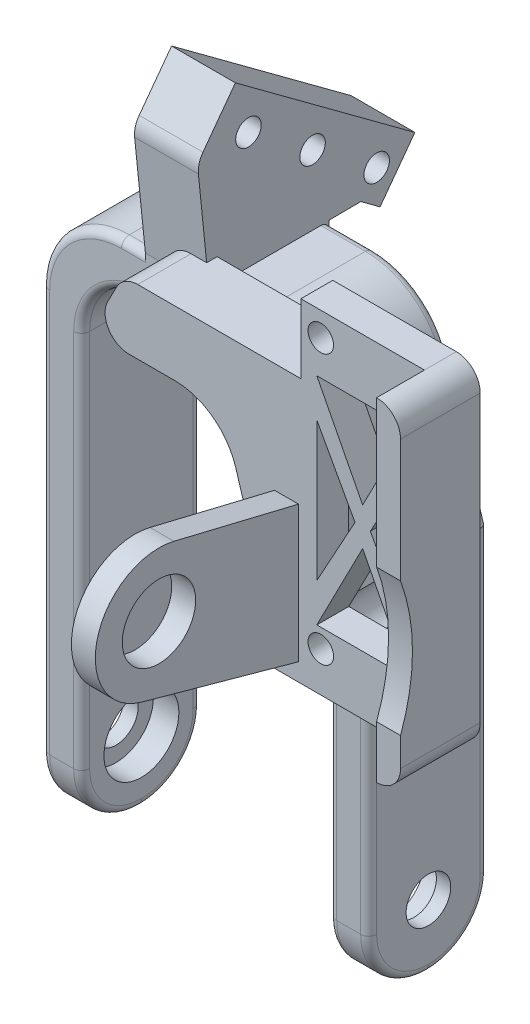
SolidWorks part; units mm, degrees
ref_plane "前视基准面" through (0, 0, 0) normal (0, 0, 1) x (1, 0, 0)
ref_plane "上视基准面" through (0, 0, 0) normal (0, 1, 0) x (1, 0, 0)
ref_plane "右视基准面" through (0, 0, 0) normal (1, 0, 0) x (0, 0, -1)
sketch "草图1" plane through (0, 0, 0) normal (0, 1, 0) x (1, 0, 0)
  line L1 (24, 7.5) -> (-17, 7.5)
  line L2 (24, 7.5) -> (24, -7.5)
  line L3 (24, -7.5) -> (-17, -7.5)
  line L4 (-17, 7.5) -> (-17, -7.5)
  line L5 (24, 7.5) -> (-17, -7.5) construction
  line L6 (24, -7.5) -> (-17, 7.5) construction
  point P0 (0, 0)
extrude "凸台-拉伸1" add sketch "草图1" against normal blind 68
sketch "草图3" plane through (0, 0, 7.5) normal (0, 0, 1) x (1, 0, 0)
  line L0 (-17, -68) -> (24, -68) construction
  line L1 (-12, -68) -> (19, -68)
  line L2 (-12, -68) -> (-12, -5)
  line L3 (-12, -5) -> (12.6087, -5)
  line L4 (19, -68) -> (19, -25.9143)
  line L5 (12.6087, -5) -> (19, -25.9143)
  line L6 (17, 0) -> (27.4891, -34.3238)
  line L7 (17, 0) -> (27.4891, 0)
  line L8 (27.4891, 0) -> (27.4891, -34.3238)
  line L9 (-17, 0) -> (24, 0) construction
  line L10 (-17, 0) -> (24, 0) construction
extrude "切除-拉伸1" cut sketch "草图3" against normal through all
fillet "圆角1" radius 8 3 edges at (-12, -5, 0) (19, -25.9143, 0) (12.6087, -5, 0)
fillet "圆角3" radius 7.5 4 edges at (21.5, -68, -7.5) (21.5, -68, 7.5) (-14.5, -68, -7.5) (-14.5, -68, 7.5)
sketch "草图4" plane through (24, 0, 0) normal (1, 0, 0) x (0, 0, -1)
  circle A0 centre (0, -60) radius 2.8
extrude "切除-拉伸2" cut sketch "草图4" against normal through all
sketch "草图6" plane through (19, 0, 0) normal (1, 0, 0) x (0, 0, -1)
  circle A0 centre (0, -60) radius 4.7
extrude "切除-拉伸4" cut sketch "草图6" along normal blind 3.2
ref_plane "基准面1" through (3.5, 0, 0) normal (1, 0, 0) x (0, 0, -1)
mirror "镜向2" about plane through (3.5, 0, 0) normal (1, 0, 0) of "切除-拉伸4"
sketch "草图7" plane through (0, 0, 0) normal (1, 0, 0) x (0, 0, -1)
  line L0 (-6.5933, 17.6444) -> (9.4891, 5.7551) construction
  line L2 (-8.9711, 14.4279) -> (-4.2154, 20.8609)
  line L3 (-4.2154, 20.8609) -> (18.3, 4.2159)
  line L5 (7.5, 0) -> (7.5, -22.9063) construction
  line L6 (7.5, 0) -> (7.5, -22.9063) construction
  line L8 (-7.5, 0) -> (7.5, 0)
  line L9 (-7.5, -5) -> (7.5, -5) construction
  line L10 (-7.5, -5) -> (7.5, -5) construction
  line L15 (7.5, 3.0644) -> (7.5, 0)
  line L16 (-8.9711, 14.4279) -> (-7.5, 0)
  line L17 (7.5, 3.0644) -> (13.933, -1.6913)
  line L18 (18.3, 4.2159) -> (13.933, -1.6913)
  circle A2 centre (5.4685, 8.7275) radius 1.6
  circle A3 centre (-2.5727, 14.6721) radius 1.6
  circle A4 centre (13.5098, 2.7828) radius 1.6
  dimension "D1" = 10
  dimension "D2" = 3.2
  dimension "D3" = 3.2
  dimension "D9" = 10
  dimension "D4" = 3
  dimension "D5" = 5
  dimension "D6" = 4
  dimension "D7" = 3.3461
  dimension "D8" = 3.0644
extrude "凸台-拉伸2" add sketch "草图7" along normal mid plane 8
chamfer "倒角1" distance 3 distance2 5 1 edges at (0, 3.0644, -7.5) first distance on face at (4.7083, -20.0817, -7.5)
fillet "圆角4" radius 10 2 edges at (17, 0, 0) (-17, 0, 0)
fillet "圆角2" radius 1 36 edges at (-17, -35.25, -7.5) (24, -41.7031, -7.5) (24, -41.7031, 7.5) (-17, -35.25, 7.5) (-9.6569, -7.3431, 7.5) (1.3441, -5, 7.5) (19, -43.8047, 7.5) (19, -43.8047, -7.5) (1.3441, -5, -7.5) (-9.6569, -7.3431, -7.5) (-12, -36.75, -7.5) (-12, -36.75, 7.5) (19, -65.8033, 5.3033) (19, -65.8033, -5.3033) (-12, -65.8033, -5.3033) (-12, -65.8033, 5.3033) (-17, -65.8033, 5.3033) (-17, -65.8033, -5.3033) (24, -65.8033, -5.3033) (24, -65.8033, 5.3033) (11.4473, -6.5694, 7.5) (16.4949, -17.7167, 7.5) (18.9122, -25.9274, 7.5) (18.9122, -25.9274, -7.5) (16.4949, -17.7167, -7.5) (11.4473, -6.5694, -7.5) (21.5814, -14.9919, -7.5) (21.5814, -14.9919, 7.5) (6.7997, 0, -7.5) (15.5481, -1.9618, -7.5) (6.7997, 0, 7.5) (15.5481, -1.9618, 7.5) (-5.5, 0, -7.5) (-14.0711, -2.9289, -7.5) (-5.5, 0, 7.5) (-14.0711, -2.9289, 7.5)
sketch "草图16" plane through (0, 0, 7.5) normal (0, 0, 1) x (1, 0, 0)
  line L0 (6.6883, -5) -> (-4, -5) construction
  line L1 (18.6507, -24.7714) -> (14.339, -10.662) construction
  line L2 (19, -60.5) -> (19, -27.1094) construction
  line L3 (24, -22.9063) -> (24, -60.5) construction
  line L4 (19.1628, -7.0775) -> (24, -22.9063) construction
  line L5 (4, 0) -> (9.5994, 0) construction
  line L6 (6.6883, -5) -> (4, -5)
  line L7 (18.6507, -24.7714) -> (14.339, -10.662)
  line L8 (19, -32.1919) -> (19, -27.1094)
  line L9 (24, -22.9063) -> (24, -32.1919)
  line L10 (19.1628, -7.0775) -> (24, -22.9063)
  line L11 (4, 0) -> (9.5994, 0)
  line L12 (4, 0) -> (4, -5)
  line L13 (19, -32.1919) -> (24, -32.1919)
  arc A0 (14.339, -10.662) -> (6.6883, -5) centre (6.6883, -13) ccw construction
  arc A1 (19, -27.1094) -> (18.6507, -24.7714) centre (11, -27.1094) ccw construction
  arc A2 (19.1628, -7.0775) -> (9.5994, 0) centre (9.5994, -10) ccw construction
  arc A3 (14.339, -10.662) -> (6.6883, -5) centre (6.6883, -13) ccw
  arc A4 (19, -27.1094) -> (18.6507, -24.7714) centre (11, -27.1094) ccw
  arc A5 (19.1628, -7.0775) -> (9.5994, 0) centre (9.5994, -10) ccw
extrude "凸台-拉伸9" add sketch "草图16" along normal mid plane 6
sketch "草图9" plane through (0, 5.6282, 10.5) normal (0, 0, 1) x (1, 0, 0)
  line L0 (30.25, 6.1718) -> (30.25, -35.6282) construction
  line L1 (30.25, -12.3625) -> (24.5016, -1.1966)
  line L2 (24.5016, -1.1966) -> (35.9984, -1.1966)
  line L3 (38, -35.6282) -> (38, 6.1718)
  line L4 (38, 6.1718) -> (22.5, 6.1718)
  line L5 (22.5, 6.1718) -> (22.5, -35.6282)
  line L6 (22.5, -35.6282) -> (38, -35.6282)
  line L7 (35.9984, -1.1966) -> (30.25, -12.3625)
  line L8 (22.5, -14.7282) -> (38, -14.7282) construction
  line L10 (35.9984, -28.2599) -> (30.25, -17.0939)
  line L11 (24.5016, -28.2599) -> (35.9984, -28.2599)
  line L12 (30.25, -17.0939) -> (24.5016, -28.2599)
  line L13 (29.2888, -14.7282) -> (24.5016, -6.0075)
  line L14 (24.5016, -6.0075) -> (24.5016, -23.449)
  line L15 (24.5016, -23.449) -> (29.2888, -14.7282)
  line L16 (35.9984, -6.0075) -> (35.9984, -23.449)
  line L17 (31.2112, -14.7282) -> (35.9984, -6.0075)
  line L18 (35.9984, -23.449) -> (31.2112, -14.7282)
  circle A0 centre (25, 3.1718) radius 1.6
  circle A1 centre (25, -30.6282) radius 1.6
  point P12 (30.25, -1.1966)
  dimension "D1" = 3.2
  dimension "D2" = 3.2
  dimension "D3" = 33.8
  dimension "D4" = 25
  dimension "D5" = 13
  dimension "D6" = 2.5
  dimension "D7" = 25
  dimension "D8" = 5
  dimension "D9" = 3
  dimension "D10" = 2.5
extrude "凸台-拉伸3" add sketch "草图9" along normal blind 4 separate body
sketch "草图10" plane through (0, 0, 10.5) normal (0, 0, 1) x (1, 0, 0)
  line L2 (0.218, 3.1156) -> (-4, -5)
  line L9 (22.5, 3.1156) -> (22.5, -30)
  line L10 (22.5, -30) -> (38, -30) construction
  line L11 (22.5, 11.8) -> (22.5, -30) construction
  line L12 (22.5, -30) -> (19, -30)
  line L13 (0.218, 3.1156) -> (22.5, 3.1156)
  line L15 (19, -27.1094) -> (19, -60.5) construction
  line L16 (14.339, -10.662) -> (18.6507, -24.7714) construction
  line L17 (-4, -5) -> (6.6883, -5) construction
  line L18 (19, -27.1094) -> (19, -30)
  line L19 (14.339, -10.662) -> (18.6507, -24.7714)
  line L20 (-4, -5) -> (6.6883, -5)
  arc A6 (19, -27.1094) -> (18.6507, -24.7714) centre (11, -27.1094) ccw construction
  arc A7 (14.339, -10.662) -> (6.6883, -5) centre (6.6883, -13) ccw construction
  arc A8 (19, -27.1094) -> (18.6507, -24.7714) centre (11, -27.1094) ccw
  arc A9 (14.339, -10.662) -> (6.6883, -5) centre (6.6883, -13) ccw
extrude "凸台-拉伸5" add sketch "草图10" along normal up to surface (4 mm away) and the other way blind 4 up to face at (26.6, 8.8, 14.5)
sketch "草图11" plane through (0, 0, 10.5) normal (0, 0, -1) x (-1, 0, 0)
  line L0 (-24, -30) -> (-38, -30) construction
  line L1 (-38, 11.8) -> (-41, 11.8)
  line L2 (-38, 11.8) -> (-38, -30)
  line L3 (-38, -30) -> (-41, -30)
  line L4 (-41, 11.8) -> (-41, -30)
  line L5 (-24, -30) -> (-38, -30) construction
  dimension "D1" = 3
extrude "凸台-拉伸6" add sketch "草图11" against normal blind 10
sketch "草图13" plane through (0, 0, 10.5) normal (0, 0, -1) x (-1, 0, 0)
  circle A0 centre (-25, -25) radius 3
extrude "切除-拉伸5" cut sketch "草图13" along normal blind 10
sketch "草图14" plane through (41, 0, 0) normal (1, 0, 0) x (0, 0, -1)
  line L0 (-20.5, -30) -> (-10.5, -30) construction
  line L2 (-19, -15) -> (-43.25, -15) construction
  line L3 (-20.5, 11.8) -> (-20.5, -30) construction
  circle A0 centre (-43.25, -15) radius 24.25
  dimension "D2" = 48.5
  dimension "D1" = 15
  dimension "D3" = 1.5
extrude "切除-拉伸6" cut sketch "草图14" against normal up to next
fillet "圆角5" radius 3 6 edges at (41, 11.8, 15.5) (41, -30, 15.5) (0.218, 3.1156, 11.1588) (0, 14.4279, 8.9711) (22.5, 3.1156, 8.5) (-4, -5, 10.5)
ref_plane "基准面2" through (22.2, 0, 0) normal (-1, 0, 0) x (0, 0, 1)
sketch "草图15" plane through (22.2, 0, 0) normal (-1, 0, 0) x (0, 0, 1)
  line L0 (14.5, -27.7885) -> (34.1335, -22.3459)
  line L1 (14.5, -30) -> (14.5, 11.8) construction
  line L2 (30.1238, -6.8861) -> (14.5, -10.662)
  line L3 (14.5, -10.662) -> (14.5, -27.7885)
  arc A0 (34.1335, -22.3459) -> (30.1238, -6.8861) centre (32, -14.6494) ccw
  circle A1 centre (32, -14.6494) radius 4.6
  dimension "D3" = 9.2
  dimension "D1" = 17.5
  dimension "D2" = 15.3506
extrude "凸台-拉伸7" add sketch "草图15" along normal blind 3
